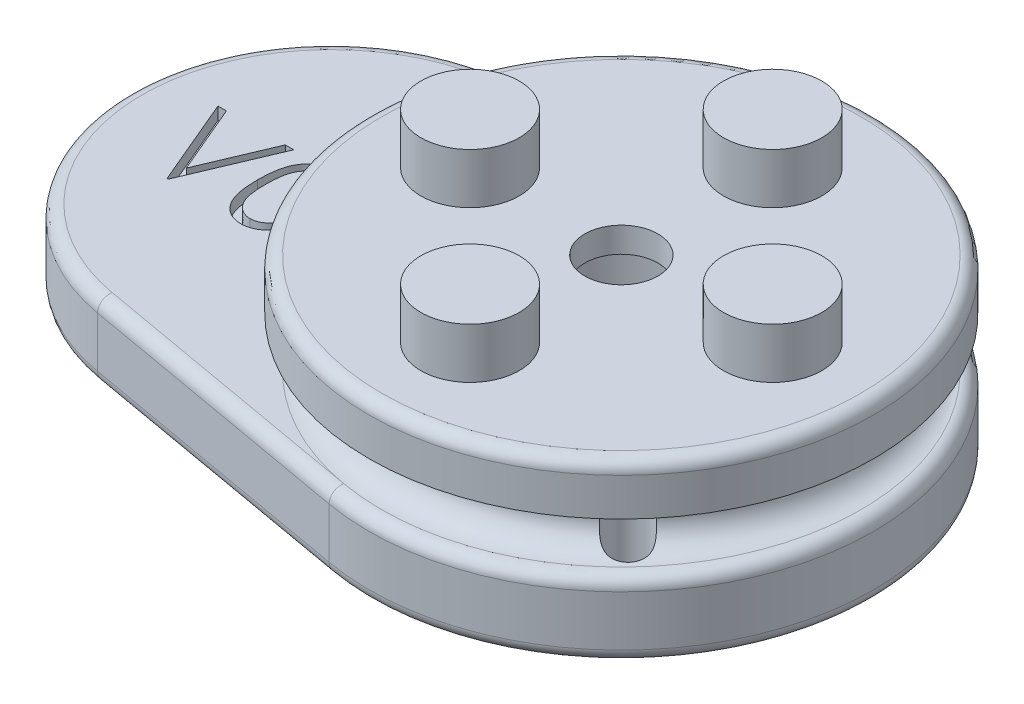
SolidWorks part; units mm, degrees
ref_plane "Front Plane" through (0, 0, 0) normal (0, 0, 1) x (1, 0, 0)
ref_plane "Top Plane" through (0, 0, 0) normal (0, 1, 0) x (1, 0, 0)
ref_plane "Right Plane" through (0, 0, 0) normal (1, 0, 0) x (0, 0, -1)
sketch "Sketch1" plane through (0, 0, 0) normal (0, 1, 0) x (1, 0, 0)
  line L0 (-12.8913, 7.8781) -> (-1.7391, 9.8476)
  line L1 (-1.7391, -9.8476) -> (-12.8913, -7.8781)
  line L2 (0, 0) -> (-11.5, 0) construction
  arc A0 (-1.7391, -9.8476) -> (-1.7391, 9.8476) centre (0, 0) ccw
  arc A1 (-12.8913, 7.8781) -> (-12.8913, -7.8781) centre (-11.5, 0) ccw
  dimension "D1" = 10
  dimension "D2" = 8
  dimension "D3" = 11.5
extrude "Boss-Extrude1" add sketch "Sketch1" along normal blind 3
sketch "Sketch2" plane through (0, 3, 0) normal (0, 1, 0) x (1, 0, 0)
  circle A0 centre (0, 0) radius 1.5
  dimension "D1" = 3
extrude "Cut-Extrude1" cut sketch "Sketch2" against normal blind 3
sketch "Sketch3" plane through (0, 3, 0) normal (0, 1, 0) x (1, 0, 0)
  circle A0 centre (0, 0) radius 8.5
  dimension "D1" = 17
extrude "Boss-Extrude2" add sketch "Sketch3" along normal blind 2
sketch "Sketch4" plane through (0, 5, 0) normal (0, 1, 0) x (1, 0, 0)
  circle A0 centre (0, 0) radius 10
extrude "Boss-Extrude3" add sketch "Sketch4" along normal blind 2
fillet "Fillet1" radius 1 2 edges at (0, 5, 8.5) (0, 3, 8.5)
sketch "Sketch6" plane through (0, 0, 0) normal (0, -1, 0) x (1, 0, 0)
  circle A0 centre (0, 0) radius 3
  dimension "D1" = 6
extrude "Cut-Extrude3" cut sketch "Sketch6" against normal through all
sketch "Sketch7" plane through (0, 0, 0) normal (0, -1, 0) x (1, 0, 0)
  circle A0 centre (0, 0) radius 6 construction
  circle A1 centre (0, 6) radius 1
  circle A2 centre (6, 0) radius 1
  circle A3 centre (0, -6) radius 1
  circle A4 centre (-6, 0) radius 1
  dimension "D1" = 12
  dimension "D2" = 2
  dimension "D3" = 2
  dimension "D4" = 2
  dimension "D5" = 2
extrude "Cut-Extrude4" cut sketch "Sketch7" against normal through all
sketch "Sketch8" plane through (0, 0, 0) normal (0, -1, 0) x (1, 0, 0)
  circle A0 centre (0, 0) radius 8.5 construction
  circle A1 centre (6.1388, 5.8792) radius 0.8
  dimension "D1" = 1.6
  dimension "D2" = 17
extrude "Cut-Extrude5" cut sketch "Sketch8" against normal through all
sketch "Sketch9" plane through (0, 3, 0) normal (0, 1, 0) x (1, 0, 0)
  text T0 "V0"
extrude "Cut-Extrude6" cut sketch "Sketch9" against normal blind 0.5
fillet "Fillet3" radius 0.5 8 edges at (-7.3152, 0, -8.8628) (10, 0, 0) (-7.3152, 0, 8.8628) (-7.3152, 3, -8.8628) (10, 3, 0) (-7.3152, 3, 8.8628) (-19.5, 0, 0) (-19.5, 3, 0)
fillet "Fillet4" radius 0.5 1 edges at (0, 7, 10)
sketch "Sketch10" plane through (0, 7, 0) normal (0, 1, 0) x (1, 0, 0)
  circle A0 centre (0, 0) radius 9.5
extrude "Boss-Extrude4" add sketch "Sketch10" against normal up to surface (2 mm away) up to face at (0, 5, 9.5)
sketch "Sketch11" plane through (0, 7, 0) normal (0, 1, 0) x (1, 0, 0)
  circle A0 centre (0, 6) radius 1.95
  dimension "D1" = 3.9
  dimension "D2" = 6
extrude "Boss-Extrude5" add sketch "Sketch11" along normal blind 2
pattern_circular "CirPattern1" count 4 over 360 about axis through (0, 7, 0) along (0, 1, 0) of "Boss-Extrude5"
sketch "Sketch12" plane through (0, 7, 0) normal (0, 1, 0) x (1, 0, 0)
  circle A0 centre (0, 0) radius 1.45
  dimension "D1" = 2.9
extrude "Cut-Extrude7" cut sketch "Sketch12" against normal through all
sketch "Sketch13" plane through (0, 5, 0) normal (0, -1, 0) x (1, 0, 0)
  circle A1 centre (0, 0) radius 3
  circle A2 centre (0, 0) radius 3
  dimension "D1" = 0
extrude "Cut-Extrude8" cut sketch "Sketch13" against normal offset from surface (1 mm away) 1 up to face at (0, 7, 1.45)
